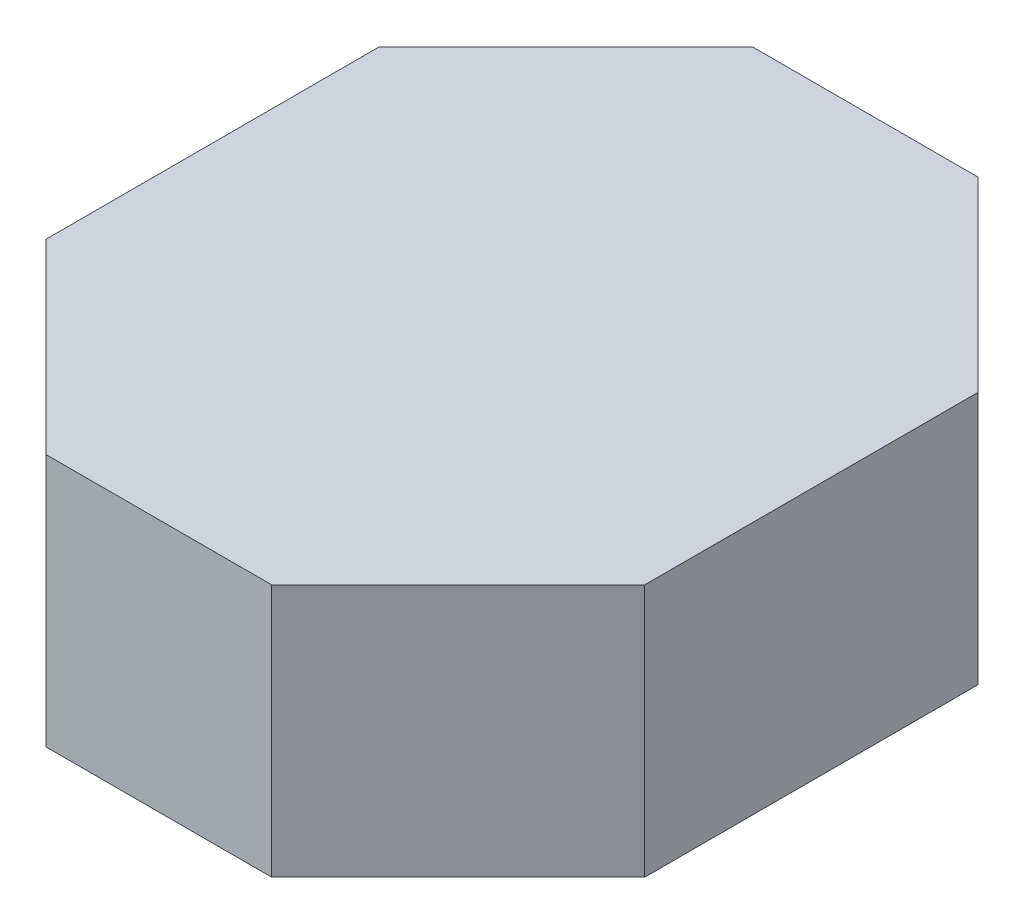
SolidWorks part; units mm, degrees
ref_plane "前视基准面" through (0, 0, 0) normal (0, 0, 1) x (1, 0, 0)
ref_plane "上视基准面" through (0, 0, 0) normal (0, 1, 0) x (1, 0, 0)
ref_plane "右视基准面" through (0, 0, 0) normal (1, 0, 0) x (0, 0, -1)
other "Configuration Table"
sketch "草图1" plane through (0, 0, 0) normal (0, 1, 0) x (1, 0, 0)
  line L0 (0, 0) -> (68, 0)
  line L1 (68, 0) -> (124.5685, -56.5685)
  line L2 (124.5685, -56.5685) -> (124.5685, -158.5685)
  line L3 (124.5685, -158.5685) -> (68, -215.1371)
  line L4 (68, -215.1371) -> (0, -215.1371)
  line L5 (0, -215.1371) -> (-56.5685, -158.5685)
  line L6 (-56.5685, -158.5685) -> (-56.5685, -56.5685)
  line L7 (-56.5685, -56.5685) -> (0, 0)
  line L8 (-1.6569, 4) -> (69.6569, 4)
  line L9 (69.6569, 4) -> (128.5685, -54.9117)
  line L10 (128.5685, -54.9117) -> (128.5685, -160.2254)
  line L11 (128.5685, -160.2254) -> (69.6569, -219.1371)
  line L12 (69.6569, -219.1371) -> (-1.6569, -219.1371)
  line L13 (-1.6569, -219.1371) -> (-60.5685, -160.2254)
  line L14 (-60.5685, -160.2254) -> (-60.5685, -54.9117)
  line L15 (-60.5685, -54.9117) -> (-1.6569, 4)
  line L16 (-58.5685, -55.7401) -> (-0.8284, 2)
  line L17 (-0.8284, 2) -> (68.8284, 2)
  line L18 (68.8284, 2) -> (126.5685, -55.7401)
  line L19 (126.5685, -55.7401) -> (126.5685, -159.397)
  line L20 (126.5685, -159.397) -> (68.8284, -217.1371)
  line L21 (68.8284, -217.1371) -> (-0.8284, -217.1371)
  line L22 (-0.8284, -217.1371) -> (-58.5685, -159.397)
  line L23 (-58.5685, -159.397) -> (-58.5685, -55.7401)
  dimension "D1" = 68
  dimension "D2" = 80
  dimension "D3" = 102
  dimension "D4" = 102
  dimension "D5" = 80
  dimension "D6" = 80
  dimension "D7" = 80
  dimension "D8" = 68
  dimension "D9" = 4
  dimension "D10" = 2
extrude "凸台-拉伸3" add sketch "草图1" along normal blind 80 contours L13 L14 L15 L8 L9 L10 L11 L12
extrude "切除-拉伸1" cut sketch "草图1<6>" along normal blind 78 contours L19 L20 L21 L22 L23 L16 L17 L18
sketch "草图1<6>" plane through (0, 0, 0) normal (0, 1, 0) x (1, 0, 0) same geometry as "草图1"
